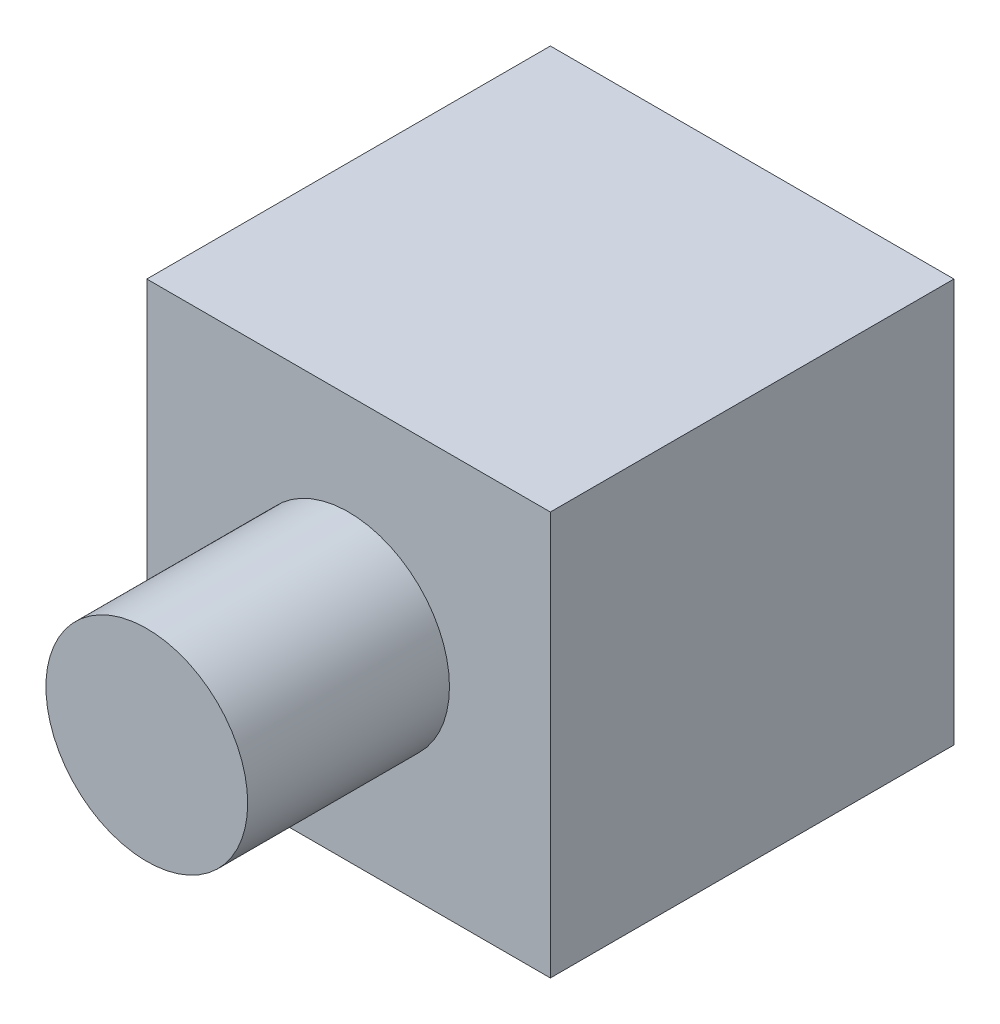
SolidWorks part; units mm, degrees
ref_plane "Front Plane" through (0, 0, 0) normal (0, 0, 1) x (1, 0, 0)
ref_plane "Top Plane" through (0, 0, 0) normal (0, 1, 0) x (1, 0, 0)
ref_plane "Right Plane" through (0, 0, 0) normal (1, 0, 0) x (0, 0, -1)
sketch "Sketch1" plane through (0, 0, 0) normal (0, 0, 1) x (1, 0, 0)
  line L0 (-101.861, 0) -> (111.7866, 0) construction
  line L1 (0, 84.9876) -> (0, -96.6501) construction
  line L3 (-50, 50) -> (50, 50)
  line L4 (-50, 50) -> (-50, -50)
  line L5 (-50, -50) -> (50, -50)
  line L6 (50, 50) -> (50, -50)
  line L7 (-50, 50) -> (50, -50) construction
  line L8 (-50, -50) -> (50, 50) construction
  point P5 (0, 0)
  dimension "D1" = 100
  dimension "D2" = 100
extrude "Boss-Extrude1" add sketch "Sketch1" along normal blind 50 and the other way blind 50
ref_plane "Plane2" through (0, 0, 100) normal (0, 0, 1) x (1, 0, 0)
sketch "Sketch2" plane through (0, 0, 100) normal (0, 0, 1) x (1, 0, 0)
  circle A0 centre (0, 0) radius 25
  dimension "D1" = 50
extrude "Boss-Extrude2" add sketch "Sketch2" against normal blind 60
ref_plane "Plane3" through (21.9186, 0, -60.2208) normal (0.342, 0, -0.9397) x (0, 1, 0)
ref_plane "Plane4" through (45.279, 0, -53.9614) normal (0.6428, 0, -0.766) x (0, 1, 0)
ref_plane "Plane5" through (59.1506, 0, -34.1506) normal (0.866, 0, -0.5) x (0, 1, 0)
ref_plane "Plane6" through (57.0428, 0, -10.0582) normal (0.9848, 0, -0.1736) x (0, 1, 0)
ref_plane "Plane7" through (39.9418, 0, 7.0428) normal (0.9848, 0, 0.1736) x (0, 1, 0)
ref_plane "Plane8" through (15.8494, 0, 9.1506) normal (0.866, 0, 0.5) x (0, 1, 0)
ref_plane "Plane9" through (-3.9614, 0, -4.721) normal (0.6428, 0, 0.766) x (0, 1, 0)
ref_plane "Plane10" through (-10.2208, 0, -28.0814) normal (0.342, 0, 0.9397) x (0, 1, 0)
ref_plane "Plane11" through (0, 0, -50) normal (0, 0, 1) x (0, 1, 0)
ref_plane "Plane12" through (21.9186, 0, -60.2208) normal (-0.342, 0, 0.9397) x (0, 1, 0)
sketch "Sketch3" plane through (57.0428, 0, -10.0582) normal (0.9848, 0, -0.1736) x (0, 1, 0)
  line L0 (-106.3527, 0) -> (128.4711, 0) construction
  line L1 (0, 104.1062) -> (0, -194.8253) construction
  line L2 (-106.3527, -50) -> (128.4711, -50) construction
  line L3 (-106.3527, -70) -> (128.4711, -70) construction
  line L5 (-10, -60) -> (10, -60)
  line L6 (-10, -60) -> (-10, -80)
  line L7 (-10, -80) -> (10, -80)
  line L8 (10, -60) -> (10, -80)
  line L9 (-10, -60) -> (10, -80) construction
  line L10 (-10, -80) -> (10, -60) construction
  point P9 (0, -70)
  point P14 (0, 0)
  dimension "D1" = 50
  dimension "D2" = 20
  dimension "D3" = 20
  dimension "D4" = 20
